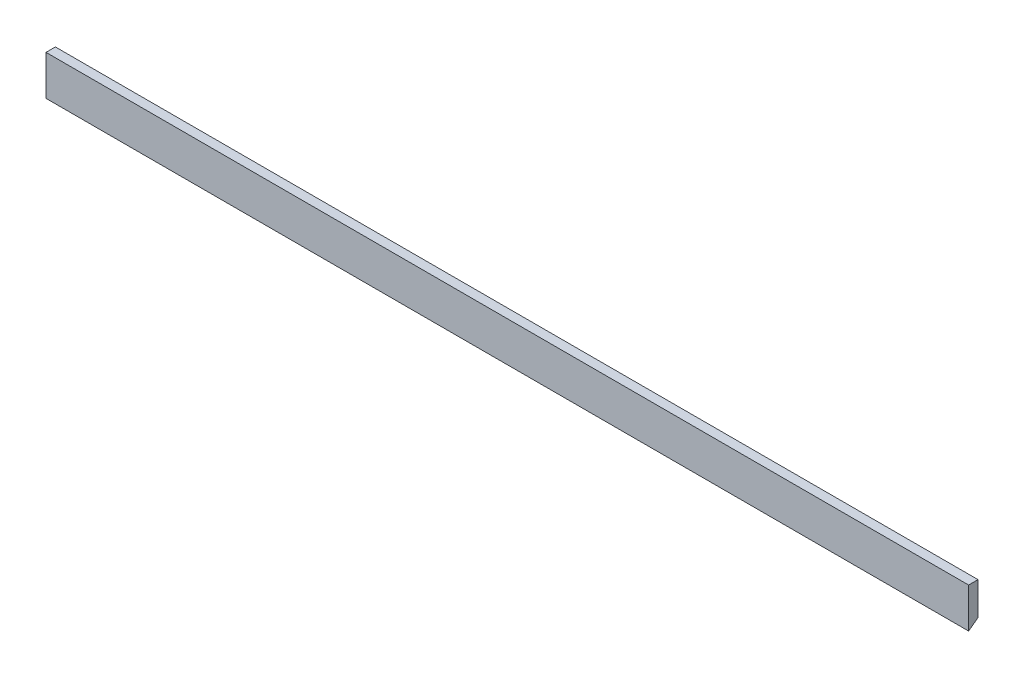
SolidWorks part; units mm, degrees
material "Balsa"
ref_plane "Front Plane" through (0, 0, 0) normal (0, 0, 1) x (1, 0, 0)
ref_plane "Top Plane" through (0, 0, 0) normal (0, 1, 0) x (1, 0, 0)
ref_plane "Right Plane" through (0, 0, 0) normal (1, 0, 0) x (0, 0, -1)
sketch "Sketch2" plane through (0, 0, 0) normal (1, 0, 0) x (0, 0, -1)
  line L1 (-1.5875, 6.745) -> (1.5875, 6.745)
  line L2 (-1.5875, 6.745) -> (-1.5875, -6.745)
  line L3 (-1.5875, -6.745) -> (1.5875, -6.745)
  line L4 (1.5875, 6.745) -> (1.5875, -6.745)
  line L5 (-1.5875, 6.745) -> (1.5875, -6.745) construction
  line L6 (-1.5875, -6.745) -> (1.5875, 6.745) construction
  point P0 (0, 0)
  dimension "D1" = 3.175
  dimension "D2" = 13.49
extrude "Boss-Extrude1" add sketch "Sketch2" along normal blind 312.1
chamfer "Chamfer1" distance 3.175 angle 36.5 1 edges at (156.05, -6.745, -1.5875) first distance on face at (156.05, -6.745, 0)
